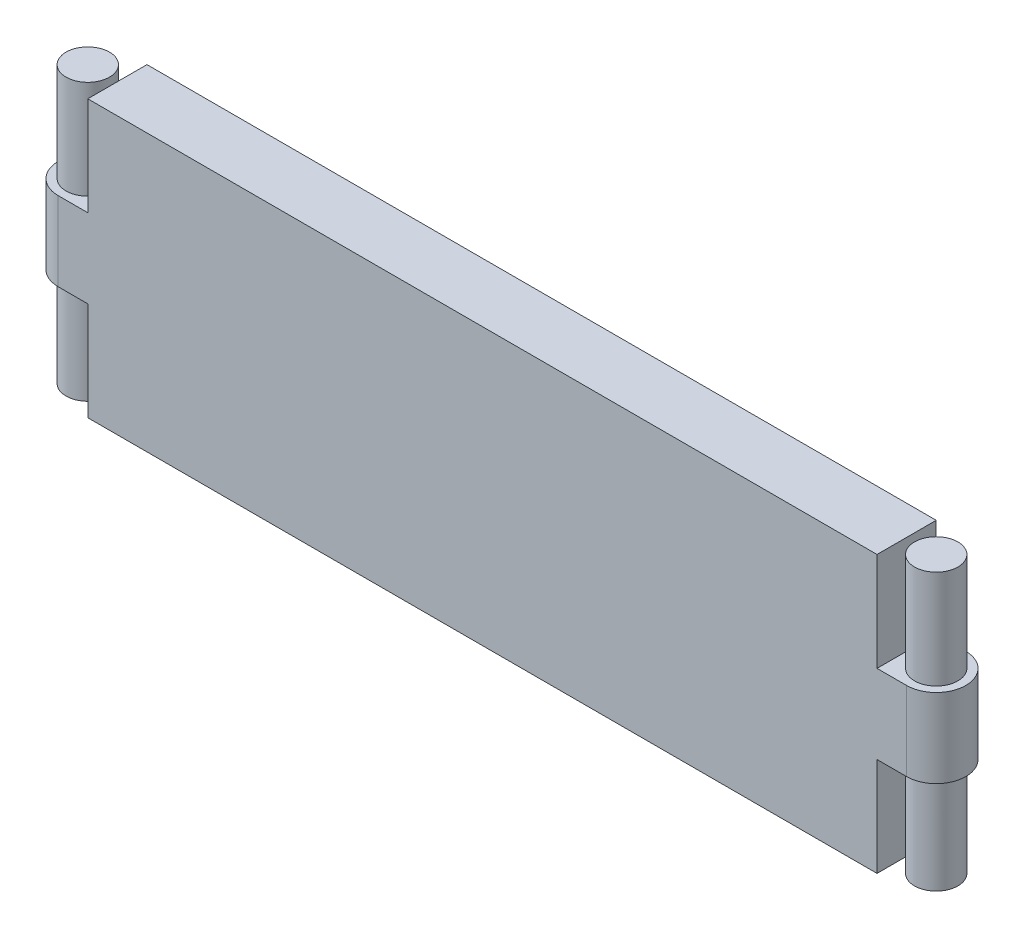
SolidWorks part; units mm, degrees
ref_plane "Front Plane" through (0, 0, 0) normal (0, 0, 1) x (1, 0, 0)
ref_plane "Top Plane" through (0, 0, 0) normal (0, 1, 0) x (1, 0, 0)
ref_plane "Right Plane" through (0, 0, 0) normal (1, 0, 0) x (0, 0, -1)
sketch "Plate Sketch" plane through (0, 0, 0) normal (0, 0, 1) x (1, 0, 0)
  line L3 (-100, 35) -> (100, 35)
  line L4 (-100, 35) -> (-100, -35)
  line L5 (-100, -35) -> (100, -35)
  line L6 (100, 35) -> (100, -35)
  line L7 (-100, 35) -> (100, -35) construction
  line L8 (-100, -35) -> (100, 35) construction
  point P2 (0, 0)
  dimension "D1" = 70
  dimension "D2" = 200
extrude "Plate Extrude" add sketch "Plate Sketch" against normal blind 15
sketch "Hinge Plate Sketch" plane through (0, 0, 0) normal (0, 1, 0) x (1, 0, 0)
  line L0 (100, 15) -> (107.5, 15)
  line L1 (107.5, 0) -> (100, 0)
  line L2 (100, 0) -> (100, 15)
  line L3 (107.5, 15) -> (107.5, 0) construction
  line L4 (100, 15) -> (-100, 15) construction
  line L6 (100, 15) -> (100, 0) construction
  line L8 (100, 0) -> (-100, 0) construction
  line L9 (107.5, 15) -> (107.5, 0) construction
  arc A0 (107.5, 0) -> (107.5, 15) centre (107.5, 7.5) ccw
  arc A1 (107.5, 15) -> (107.5, 0) centre (107.5, 7.5) ccw construction
extrude "Hinge Plate Extrude" add sketch "Hinge Plate Sketch" along normal blind 10 and the other way blind 10
sketch "Pin Sketch" plane through (0, 10, 0) normal (0, 1, 0) x (1, 0, 0)
  circle A0 centre (107.5, 7.5) radius 5.5
  arc A1 (107.5, 0) -> (107.5, 15) centre (107.5, 7.5) ccw construction
  dimension "D1" = 2
extrude "Upper Pin Extrude" add sketch "Pin Sketch" along normal up to surface (25 mm away) up to face at (0, 35, -7.5)
extrude "Lower Pin Extrude" add sketch "Pin Sketch<2>" against normal up to surface (45 mm away) from surface up to face at (0, -35, -7.5) starting at face at (105.625, -10, -7.5)
sketch "Pin Sketch<2>" plane through (0, 10, 0) normal (0, 1, 0) x (1, 0, 0) same geometry as "Pin Sketch"
mirror "Hinge Mirror" about plane through (0, 0, 0) normal (1, 0, 0) of "Lower Pin Extrude", "Upper Pin Extrude", "Hinge Plate Extrude"
